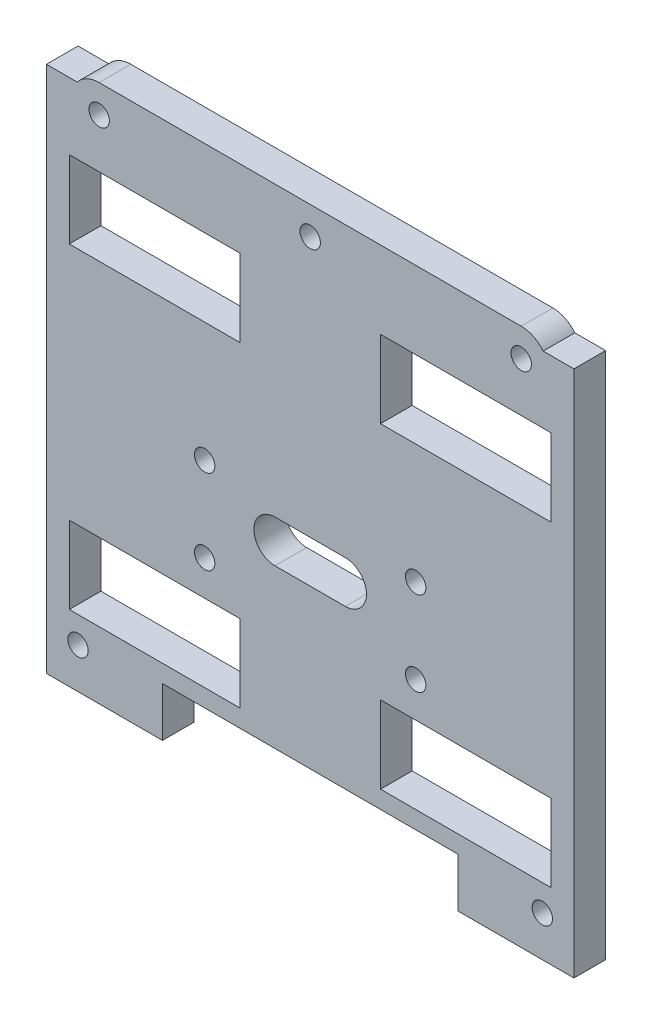
SolidWorks part; units mm, degrees
ref_plane "Front Plane" through (0, 0, 0) normal (0, 0, 1) x (1, 0, 0)
ref_plane "Top Plane" through (0, 0, 0) normal (0, 1, 0) x (1, 0, 0)
ref_plane "Right Plane" through (0, 0, 0) normal (1, 0, 0) x (0, 0, -1)
sketch "Sketch1" plane through (0, 0, 0) normal (0, 0, 1) x (1, 0, 0)
  line L0 (0, -37.5) -> (0, 37.5) construction
  line L1 (-47.5, -37.5) -> (47.5, -37.5)
  line L2 (-47.5, -37.5) -> (-47.5, 37.5)
  line L3 (-47.5, 37.5) -> (47.5, 37.5)
  line L4 (47.5, -37.5) -> (47.5, 37.5)
  line L5 (-47.5, -37.5) -> (47.5, 37.5) construction
  line L6 (-47.5, 37.5) -> (47.5, -37.5) construction
  line L7 (-47.5, 0) -> (47.5, 0) construction
  line L8 (-47.5, 22.5) -> (47.5, 22.5) construction
  line L9 (34.25, 17) -> (10, 28) construction
  line L10 (-34.25, 28) -> (-10, 28)
  line L11 (-34.25, 28) -> (-34.25, 17)
  line L12 (-34.25, 17) -> (-10, 17)
  line L13 (-10, 28) -> (-10, 17)
  line L14 (-34.25, 28) -> (-10, 17) construction
  line L15 (-34.25, 17) -> (-10, 28) construction
  line L16 (34.25, 28) -> (10, 17) construction
  line L17 (10, 28) -> (10, 17)
  line L18 (34.25, 17) -> (10, 17)
  line L19 (34.25, 28) -> (34.25, 17)
  line L20 (34.25, 28) -> (10, 28)
  line L21 (34.25, -28) -> (10, -17) construction
  line L22 (-34.25, -17) -> (-10, -28) construction
  line L23 (-34.25, -28) -> (-10, -17) construction
  line L24 (34.25, -17) -> (10, -28) construction
  line L25 (34.25, -28) -> (10, -28)
  line L26 (34.25, -28) -> (34.25, -17)
  line L27 (34.25, -17) -> (10, -17)
  line L28 (10, -28) -> (10, -17)
  line L29 (-10, -28) -> (-10, -17)
  line L30 (-34.25, -17) -> (-10, -17)
  line L31 (-34.25, -28) -> (-34.25, -17)
  line L32 (-34.25, -28) -> (-10, -28)
  point P0 (0, 0)
  point P12 (-22.125, 22.5)
  point P21 (22.125, 22.5)
  point P30 (22.125, -22.5)
  point P31 (-22.125, -22.5)
  dimension "D1" = 95
  dimension "D2" = 75
  dimension "D3" = 22.5
  dimension "D4" = 24.25
  dimension "D5" = 11
  dimension "D6" = 10
extrude "Boss-Extrude1" add sketch "Sketch1" along normal blind 4.5
sketch "Sketch8" plane through (0, 0, 4.5) normal (0, 0, 1) x (1, 0, 0)
  line L0 (-47.5, 37.5) -> (-47.5, -37.5) construction
  line L1 (47.5, -37.5) -> (47.5, 37.5) construction
  circle A0 centre (-47.5, 29.5) radius 8
  circle A1 centre (47.5, 29.5) radius 8
  dimension "D1" = 16
extrude "Boss-Extrude2" [suppressed] add sketch "Sketch8" against normal through all
sketch "Sketch2" plane through (0, 0, 4.5) normal (0, 0, 1) x (1, 0, 0)
  line L0 (0, -37.5) -> (0, 37.5) construction
  line L1 (-47.5, -37.5) -> (47.5, -37.5) construction
  line L2 (47.5, 37.5) -> (-47.5, 37.5) construction
  line L3 (-47.5, 0) -> (47.5, 0) construction
  line L4 (-47.5, 37.5) -> (-47.5, -37.5) construction
  line L5 (47.5, -37.5) -> (47.5, 37.5) construction
  line L6 (-40, 0) -> (40, 0) construction
  line L7 (-30, 35) -> (30, 35) construction
  circle A0 centre (-30, 35) radius 1.45
  circle A1 centre (30, 35) radius 1.45
  circle A2 centre (40, 0) radius 1.45
  circle A3 centre (-40, 0) radius 1.45
  circle A4 centre (0, 35) radius 1.45
  dimension "D1" = 2.9
  dimension "D7" = 2.9
  dimension "D8" = 2.9
  dimension "D9" = 2.9
  dimension "D2" = 30
  dimension "D3" = 35
  dimension "D4" = 80
  dimension "D5" = 40
  dimension "D6" = 0
extrude "screwHoles" cut sketch "Sketch2" against normal through all
sketch "Sketch3" plane through (0, 0, 4.5) normal (0, 0, 1) x (1, 0, 0)
  line L0 (-47.5, -20) -> (26.0486, -20) construction
  line L1 (-47.5, 37.5) -> (-47.5, -37.5) construction
  line L3 (0, 37.5) -> (0, -37.5) construction
  line L4 (47.5, 37.5) -> (-47.5, 37.5) construction
  line L5 (-47.5, -37.5) -> (47.5, -37.5) construction
  line L6 (18.95, -22.2) -> (9.05, -17.8) construction
  line L7 (-18.95, -17.8) -> (-9.05, -17.8)
  line L8 (-18.95, -17.8) -> (-18.95, -22.2)
  line L9 (-18.95, -22.2) -> (-9.05, -22.2)
  line L10 (-9.05, -17.8) -> (-9.05, -22.2)
  line L11 (-18.95, -17.8) -> (-9.05, -22.2) construction
  line L12 (-18.95, -22.2) -> (-9.05, -17.8) construction
  line L13 (18.95, -17.8) -> (9.05, -22.2) construction
  line L14 (9.05, -17.8) -> (9.05, -22.2)
  line L15 (18.95, -22.2) -> (9.05, -22.2)
  line L16 (18.95, -17.8) -> (18.95, -22.2)
  line L17 (18.95, -17.8) -> (9.05, -17.8)
  line L18 (-47.5, 37.5) -> (-47.5, -37.5) construction
  point P2 (-47.5, 0)
  point P12 (-14, -20)
  point P21 (14, -20)
  dimension "D1" = 9.9
  dimension "D3" = 14
  dimension "D4" = 20
extrude "BeltClamp" [suppressed] cut sketch "Sketch3" against normal through all
sketch "Sketch4" plane through (0, 0, 4.5) normal (0, 0, 1) x (1, 0, 0)
  line L0 (-47.5, 0) -> (47.5, 0) construction
  line L1 (-47.5, 37.5) -> (-47.5, -37.5) construction
  line L2 (47.5, -37.5) -> (47.5, 37.5) construction
  line L3 (0, 0) -> (0, 33.55) construction
  line L4 (-29.85, 2.175) -> (-20.15, 2.175)
  line L5 (-29.85, 2.175) -> (-29.85, -2.175)
  line L6 (-29.85, -2.175) -> (-20.15, -2.175)
  line L7 (-20.15, 2.175) -> (-20.15, -2.175)
  line L8 (-29.85, 2.175) -> (-20.15, -2.175) construction
  line L9 (-29.85, -2.175) -> (-20.15, 2.175) construction
  line L10 (29.85, -2.175) -> (20.15, 2.175) construction
  line L11 (29.85, 2.175) -> (20.15, -2.175) construction
  line L12 (20.15, 2.175) -> (20.15, -2.175)
  line L13 (29.85, -2.175) -> (20.15, -2.175)
  line L14 (29.85, 2.175) -> (29.85, -2.175)
  line L15 (29.85, 2.175) -> (20.15, 2.175)
  line L16 (-29.85, -2.175) -> (-20.15, 2.175) construction
  circle A0 centre (-40, 0) radius 1.45 construction
  circle A1 centre (0, 35) radius 1.45 construction
  point P6 (-25, 0)
  point P22 (25, 0)
  dimension "D3" = 0
  dimension "D2" = 4.35
  dimension "D4" = 25
extrude "Cut-Extrude3" [suppressed] cut sketch "Sketch4" against normal through all
sketch "Sketch5" plane through (0, 0, 4.5) normal (0, 0, 1) x (1, 0, 0)
  line L0 (-47.5, -9.75) -> (47.5, -9.75) construction
  line L1 (-47.5, 37.5) -> (-47.5, -37.5) construction
  line L2 (47.5, -37.5) -> (47.5, 37.5) construction
  line L4 (0, -37.5) -> (0, 37.5) construction
  line L5 (-47.5, -37.5) -> (47.5, -37.5) construction
  line L6 (47.5, 37.5) -> (-47.5, 37.5) construction
  line L7 (-30.825, -14.6) -> (-35.175, -4.9) construction
  line L8 (30.825, -4.9) -> (35.175, -4.9)
  line L9 (30.825, -4.9) -> (30.825, -14.6)
  line L10 (30.825, -14.6) -> (35.175, -14.6)
  line L11 (35.175, -4.9) -> (35.175, -14.6)
  line L12 (30.825, -4.9) -> (35.175, -14.6) construction
  line L13 (30.825, -14.6) -> (35.175, -4.9) construction
  line L14 (-30.825, -4.9) -> (-35.175, -14.6) construction
  line L15 (-35.175, -4.9) -> (-35.175, -14.6)
  line L16 (-30.825, -14.6) -> (-35.175, -14.6)
  line L17 (-30.825, -4.9) -> (-30.825, -14.6)
  line L18 (-30.825, -4.9) -> (-35.175, -4.9)
  line L19 (33, -9.75) -> (33, -37.5) construction
  line L20 (-33, -9.75) -> (-33, -37.5) construction
  line L21 (-33, -31.75) -> (33, -31.75) construction
  circle A0 centre (33, -31.75) radius 1.45
  circle A1 centre (-33, -31.75) radius 1.45
  point P15 (33, -9.75)
  point P24 (-33, -9.75)
  dimension "D5" = 2.9
  dimension "D2" = 9.7
  dimension "D3" = 4.35
  dimension "D4" = 33
  dimension "D6" = 22
  dimension "D1" = 9.75
extrude "Cut-Extrude4" [suppressed] cut sketch "Sketch5" against normal through all
sketch "Sketch9" plane through (0, 0, 4.5) normal (0, 0, 1) x (1, 0, 0)
  line L0 (47.5, 37.5) -> (-47.5, 37.5) construction
  line L1 (0, 37.5) -> (0, -37.5) construction
  line L2 (-47.5, -37.5) -> (47.5, -37.5) construction
  line L3 (50.5, 35) -> (45.5, 35) construction
  line L4 (-50.5, 35) -> (-45.5, 35) construction
  circle A0 centre (-30, 35) radius 4
  circle A1 centre (-30, 35) radius 1.45
  circle A2 centre (-30, 35) radius 1.45 construction
  circle A3 centre (30, 35) radius 1.45
  circle A4 centre (30, 35) radius 4
  point P17 (0, -37.5)
  dimension "D1" = 8
extrude "Boss-Extrude3" add sketch "Sketch9" against normal through all
sketch "Sketch10" plane through (0, 0, 4.5) normal (0, 0, 1) x (1, 0, 0)
  line L0 (-60, 37.5) -> (-37.5, 37.5)
  line L1 (-37.5, 37.5) -> (-37.5, -37.5)
  line L2 (-47.5, -37.5) -> (47.5, -37.5) construction
  line L3 (-37.5, -37.5) -> (-60, -37.5)
  line L4 (-60, -37.5) -> (-60, 37.5)
  line L5 (0, 37.5) -> (0, -37.5) construction
  line L6 (26.8775, 37.5) -> (-26.8775, 37.5) construction
  line L7 (60, -37.5) -> (60, 37.5)
  line L8 (37.5, -37.5) -> (60, -37.5)
  line L9 (37.5, 37.5) -> (37.5, -37.5)
  line L10 (60, 37.5) -> (37.5, 37.5)
  line L11 (-60, -37.5) -> (-60, 37.5)
  line L12 (-33.1225, 37.5) -> (-47.5, 37.5) construction
  line M3 (47.5, -37.5) -> (47.5, 37.5)
  line M7 (-47.5, 37.5) -> (-47.5, -37.5)
  line M8 (-47.5, -37.5) -> (47.5, -37.5)
  dimension "D3" = 0
  dimension "D1" = 75
  dimension "D2" = 60
extrude "Cut-Extrude5" cut sketch "Sketch10" against normal through all contours L1 L0 M7 M8 | L10 L9 M3 M8 region at (42.5, 0, 4.5) region at (-42.5, 0, 4.5)
sketch "Sketch11" plane through (0, 0, 4.5) normal (0, 0, 1) x (1, 0, 0)
  line L0 (-30, 39) -> (30, 39)
  line L1 (30, 39) -> (26.8775, 37.5)
  line L2 (26.8775, 37.5) -> (-26.8775, 37.5)
  line L3 (-26.8775, 37.5) -> (-30, 39)
  arc A0 (-26.8775, 37.5) -> (-33.1225, 37.5) centre (-30, 35) ccw construction
  arc A1 (33.1225, 37.5) -> (26.8775, 37.5) centre (30, 35) ccw construction
extrude "Boss-Extrude4" add sketch "Sketch11" against normal through all
sketch "Sketch12" plane through (0, 0, 4.5) normal (0, 0, 1) x (1, 0, 0)
  line L0 (-37.5, -12) -> (37.5, -12) construction
  line L1 (-37.5, 37.5) -> (-37.5, -37.5) construction
  line L2 (37.5, 37.5) -> (37.5, -37.5) construction
  line L3 (0, 0) -> (0, -37.5) construction
  line L4 (-37.5, -37.5) -> (37.5, -37.5) construction
  circle A0 centre (-15, -12) radius 1.45
  circle A1 centre (15, -12) radius 1.45
  dimension "D2" = 2.9
  dimension "D1" = 15
  dimension "D3" = 12
extrude "FanBraceScrews" cut sketch "Sketch12" against normal through all
sketch "Sketch13" plane through (0, 0, 4.5) normal (0, 0, 1) x (1, 0, 0)
  line L0 (-37.5, -37.5) -> (37.5, -37.5) construction
  line L1 (-21, -44.5) -> (21, -44.5)
  line L2 (-21, -44.5) -> (-21, -30.5)
  line L3 (-21, -30.5) -> (21, -30.5)
  line L4 (21, -44.5) -> (21, -30.5)
  line L5 (-21, -44.5) -> (21, -30.5) construction
  line L6 (-21, -30.5) -> (21, -44.5) construction
  point P0 (0, -37.5)
  dimension "D1" = 42
  dimension "D2" = 7
extrude "Cut-Extrude7" cut sketch "Sketch13" against normal through all
sketch "Sketch20" plane through (0, 0, 0) normal (0, 0, -1) x (-1, 0, 0)
  line L0 (15, -10.55) -> (15, 0) construction
  line L1 (0, 0) -> (0, 8.2059) construction
  line L2 (-15, -10.55) -> (-15, 0) construction
  circle A0 centre (15, -12) radius 1.45 construction
  circle A1 centre (15, 0) radius 1.45
  circle A2 centre (-15, 0) radius 1.45
  dimension "D1" = 12
extrude "Cut-Extrude11" cut sketch "Sketch20" against normal through all
sketch "Sketch14" plane through (0, 0, 4.5) normal (0, 0, 1) x (1, 0, 0)
  line L0 (15, -13.45) -> (15, 0) construction
  line L1 (0, 0) -> (0, -40.3958) construction
  line L2 (-15, -13.45) -> (-15, 0) construction
  circle A0 centre (15, -12) radius 1.45 construction
  circle A1 centre (15, 0) radius 1.45
  circle A2 centre (-15, 0) radius 1.45
  dimension "D2" = 2.9
  dimension "D1" = 12
extrude "Cut-Extrude8" [suppressed] cut sketch "Sketch14" against normal through all
sketch "Sketch15" plane through (0, 0, 4.5) normal (0, 0, 1) x (1, 0, 0)
  line L0 (-25, 1.5) -> (-25, -10.5) construction
  line L2 (0, 0) -> (0, -11.0705) construction
  line L3 (16, -8.3509) -> (25, -10.5) construction
  line L4 (25, 1.5) -> (25, -10.5) construction
  circle A0 centre (-25, 1.5) radius 1.45
  circle A1 centre (-25, -10.5) radius 1.45
  circle A2 centre (25, -10.5) radius 1.45
  circle A3 centre (25, 1.5) radius 1.45
  circle A5 centre (-15, -12) radius 1.45 construction
  dimension "D1" = 12
  dimension "D3" = 2.9
  dimension "D4" = 2.9
  dimension "D2" = 25
  dimension "D5" = 1.5
extrude "BeltClipScrews" [suppressed] cut sketch "Sketch15" against normal through all
sketch "Sketch16" [suppressed] plane through (0, 0, 4.5) normal (0, 0, 1) x (1, 0, 0)
  line L0 (0, 0) -> (0, -11.3016) construction
  line L1 (-29.85, 2.175) -> (-20.15, 2.175)
  line L2 (-29.85, 2.175) -> (-29.85, -2.175)
  line L3 (-29.85, -2.175) -> (-20.15, -2.175)
  line L4 (-20.15, 2.175) -> (-20.15, -2.175)
  line L5 (-35.175, -4.9) -> (-30.825, -4.9)
  line L6 (-35.175, -4.9) -> (-35.175, -14.6)
  line L7 (-35.175, -14.6) -> (-30.825, -14.6)
  line L8 (-30.825, -4.9) -> (-30.825, -14.6)
  line L9 (30.825, -4.9) -> (30.825, -14.6)
  line L10 (35.175, -14.6) -> (30.825, -14.6)
  line L11 (35.175, -4.9) -> (35.175, -14.6)
  line L12 (35.175, -4.9) -> (30.825, -4.9)
  line L13 (20.15, 2.175) -> (20.15, -2.175)
  line L14 (29.85, -2.175) -> (20.15, -2.175)
  line L15 (29.85, 2.175) -> (29.85, -2.175)
  line L16 (29.85, 2.175) -> (20.15, 2.175)
  line L17 (-30.825, -4.9) -> (-30.825, -14.6)
extrude "Boss-Extrude5" [suppressed] add sketch "Sketch16" against normal through all contours L8 L5 L6 L7 | L4 L1 L2 L3 | L15 L16 L13 L14 | L11 L12 L9 L10
sketch "Sketch17" [suppressed] plane through (0, 0, 4.5) normal (0, 0, 1) x (1, 0, 0)
  line L0 (0, -30.5) -> (0, 0) construction
  line L1 (21, -30.5) -> (-21, -30.5) construction
  line L2 (-37.5, -37.5) -> (-46.5, -37.5)
  line L3 (-46.5, -37.5) -> (-46.5, -22.5)
  line L4 (-46.5, -22.5) -> (-43.5, -22.5)
  line L5 (-43.5, -22.5) -> (-43.5, -32.5)
  line L6 (-43.5, -32.5) -> (-37.5, -32.5)
  line L7 (-37.5, 37.5) -> (-37.5, -37.5) construction
  line L8 (-37.5, -32.5) -> (-37.5, -37.5)
  line L9 (-37.5, -37.5) -> (-37.5303, -37.4889)
  dimension "D1" = 3
  dimension "D2" = 6
  dimension "D3" = 5
  dimension "D4" = 15
extrude "Boss-Extrude6" [suppressed] add sketch "Sketch17" against normal through all contours L8 L6 L5 L4 L3 L2
sketch "Sketch18" plane through (0, 0, 0) normal (0, 0, 1) x (1, 0, 0)
  line L0 (0, -30.5) -> (0, 0) construction
  line L1 (-37.5, -37.5) -> (-21, -37.5) construction
  line L7 (-37.5, -27.5) -> (-37.5, -22.5)
  line L9 (-43.5, -27.5) -> (-37.5, -27.5)
  line L10 (-37.5, -30) -> (-45.5, -30) construction
  line L11 (-37.5, 37.5) -> (-37.5, -37.5) construction
  line L12 (-43.5, -37.5) -> (-43.5, -27.5)
  line L13 (-46.5, -37.5) -> (-43.5, -37.5)
  line L14 (-46.5, -22.5) -> (-46.5, -37.5)
  line L15 (-37.5, -22.5) -> (-46.5, -22.5)
  dimension "D1" = 6
  dimension "D2" = 15
  dimension "D3" = 5
extrude "Boss-Extrude7" [suppressed] add sketch "Sketch18" along normal through all
mirror "Mirror1" [suppressed] about plane through (0, 0, 0) normal (1, 0, 0)
fillet "Fillet1" [suppressed] radius 2
mirror "Mirror2" [suppressed] about plane through (0, 0, 0) normal (1, 0, 0)
fillet "Fillet2" [suppressed] radius 2
sketch "Sketch19" plane through (0, 0, 4.5) normal (0, 0, 1) x (1, 0, 0)
  line L0 (-5, -5) -> (5, -5) construction
  line L1 (-5, -2) -> (5, -2)
  line L2 (-5, -8) -> (5, -8)
  line L3 (0, 0) -> (0, -15.8058) construction
  arc A0 (-5, -2) -> (-5, -8) centre (-5, -5) ccw
  arc A1 (5, -8) -> (5, -2) centre (5, -5) ccw
  point P2 (0, -5)
  dimension "D1" = 10
  dimension "D2" = 6
  dimension "D3" = 0
  dimension "D4" = 5
extrude "Cut-Extrude9" cut sketch "Sketch19" against normal through all
sketch "Sketch21" plane through (0, 0, 0) normal (0, 0, -1) x (-1, 0, 0)
  line L0 (0, 0) -> (0, -30.5) construction
  line L1 (-21, -30.5) -> (21, -30.5) construction
  circle A0 centre (-33, -31.75) radius 1.45
  circle A1 centre (33, -31.75) radius 1.45
  dimension "D1" = 2.9
  dimension "D2" = 33
  dimension "D3" = 31.75
extrude "Cut-Extrude12" cut sketch "Sketch21" against normal through all
equation "\"X-ROD-SPACING\"=45"
equation "\"Y-ROD-SPACING\"=75"
equation "\"Z-ROD-SPACING\"=17.5"
equation "\"Y-BED-OFFSET\"=2"
equation "\"Y-BED-ROD-INSET\"=3.5"
equation "\"Y-BED-SCREW-SPACING\"=209"
equation "\"Y-BED-SCREW-CUTOUT-SLOT-HEIGHT\"=2.5"
equation "\"T-SLOT-NUT-FILLET-RADIUS\"=0.5"
equation "\"T-SLOT-SCREW-SHAFT-RADIUS\"=1.55"
equation "\"T-SLOT-SCREW-SHAFT-CUTOUT-LENGTH\"=11"
equation "\"T-SLOT-NUT-DEPTH\"=3.5"
equation "\"T-SLOT-NUT-WIDTH\"=2.85"
equation "\"T-SLOT-NUT-END-DISTANCE\"=8"
equation "\"ACRYLIC-THICKNESS\"=10"
equation "\"ACRYLIC-THICKNESS2\"=4.5"
equation "\"ACRYLIC-TAB-CUTOUT-SIZE\"=\"ACRYLIC-THICKNESS\"+\"ACRYLIC-TAB-TOLERANCE\"*2"
equation "\"ACRYLIC-TAB-WIDTH\"=\"ACRYLIC-THICKNESS\""
equation "\"ACRYLIC-M3-HOLE\"=2.9"
equation "\"SMOOTHROD-CAP-SCREW-DISTANCE\"=20"
equation "\"FRAME-WIDTH-INNER\"=370"
equation "\"NEMA17-HOLE-SPACING\"=31"
equation "\"NEMA17-CENTRAL-CUTOUT\"=22.5"
equation "\"Z-BRACKET-REACH\"=57"
equation "\"Z-ROD-INSET\"=13.5"
equation "\"TOP-BRACKET-SPACING\"=40"
equation "\"SMOOTHROD-X-LENGTH\"=350"
equation "\"SMOOTHROD-Y-LENGTH\"=350"
equation "\"SMOOTHROD-Z-LENGTH\"=350"
equation "\"SMOOTHROD-TIGHTENING-HEADROOM\"=.25"
equation "\"LEADSCREW-Z-LENGTH\"=300"
equation "\"SCREW-LENGTH-FRAME\"=\"ACRYLIC-THICKNESS\" + 10"
equation "\"SCREW-LENGTH-MOTOR\"=\"ACRYLIC-THICKNESS\" + 5"
equation "\"SCREW-HEAD-RADIUS\"=6"
equation "\"PRINTED-X-SMOOTHROD-DIAMETER\"=8.8"
equation "\"PRINTED-X-SMOOTHROD-CUTOUT\"=10"
equation "\"PRINTED-X-BASE-HEIGHT\"=10"
equation "\"PRINTED-LM8UU-CUTOUT-SIZE\"=15.5"
equation "\"PRINTED-LM8UU-CUTOUT-LENGTH\"=24.5"
equation "\"PRINTED-X-IDLER-HEIGHT\"=16"
equation "\"PSU-MOUNTING-WIDTH\"=50"
equation "\"PSU-MOUNTING-HEIGHT\"=150"
equation "\"Y-BELT-TO-ROD-DISTANCE\"=20"
equation "\"SPOOL-HOLDER-ROD-SPACING\"=150"
equation "\"D3@Sketch1\"=\"X-ROD-SPACING\"/2"
equation "\"D4@Sketch1\"=\"ACRYLIC-X-CARRIAGE-LM8UU-CUTOUT-WIDTH\""
equation "\"D1@Boss-Extrude1\"=\"ACRYLIC-THICKNESS2\""
equation "\"D1@Sketch2\"=\"ACRYLIC-M3-HOLE\""
equation "\"D1@Sketch3\"=\"ACRYLIC-TAB-CUTOUT-SIZE\""
equation "\"D2@Sketch3\"=\"ACRYLIC-THICKNESS2\"+\"ACRYLIC-TAB-TOLERANCE\"*2"
equation "\"ACRYLIC-X-CARRIAGE-WIDTH\"=55"
equation "\"ACRYLIC-X-CARRIAGE-HEIGHT\"=75"
equation "\"D2@Sketch1\"=\"ACRYLIC-X-CARRIAGE-HEIGHT\""
equation "\"ACRYLIC-X-CARRIAGE-CENTER-TAB-SPACING\"=14"
equation "\"D3@Sketch3\"=\"ACRYLIC-X-CARRIAGE-CENTER-TAB-SPACING\""
equation "\"SCREW-LENGTH-EXTRUDER\"=28"
equation "\"ACRYLIC-X-CARRIAGE-SCREW-SPACING-X\"=15"
equation "\"ACRYLIC-X-CARRIAGE-SCREW-SPACING-Y\"=33"
equation "\"D1@Sketch4\"=\"ACRYLIC-TAB-WIDTH\"-\"KERF\"*4"
equation "\"D2@Sketch4\"=\"ACRYLIC-THICKNESS2\"-\"KERF\"*2"
equation "\"D2@Sketch5\"=\"ACRYLIC-TAB-WIDTH\"-\"KERF\"*4"
equation "\"D3@Sketch5\"=\"ACRYLIC-THICKNESS2\"-\"KERF\"*2"
equation "\"ACRYLIC-X-CARRIAGE-EXTRUDER-SHELF-DEPTH\"=\"ACRYLIC-X-CARRIAGE-EXTRUDER-OFFSET\" + 28"
equation "\"ACRYLIC-X-CARRIAGE-EXTRUDER-BRACE-SPACING\"=23"
equation "\"D4@Sketch5\"=\"ACRYLIC-X-CARRIAGE-DUAL-MOUNT-BRACE-WIDTH\""
equation "\"D1@Sketch5\"=\"ACRYLIC-THICKNESS2\"/2 + 7.5"
equation "\"D4@Sketch2\"=\"ACRYLIC-X-CARRIAGE-DUAL-MOUNT-SCREW-WIDTH\"*2"
equation "\"D5@Sketch2\"=\"ACRYLIC-X-CARRIAGE-DUAL-MOUNT-SCREW-WIDTH\""
equation "\"D7@Sketch2\"=\"ACRYLIC-M3-HOLE\""
equation "\"D8@Sketch2\"=\"ACRYLIC-M3-HOLE\""
equation "\"ACRYLIC-X-CARRIAGE-LM8UU-CUTOUT-WIDTH\"=24.25"
equation "\"ACRYLIC-TAB-TOLERANCE\"=-.05"
equation "\"ACRYLIC-X-CARRIAGE-EXTRUDER-OFFSET\"=26"
equation "\"ACRYLIC-X-CARRIAGE-EXTRUDER-ANGLE\"=90"
equation "\"ACRYLIC-X-CARRIAGE-EXTRUDER-BRACE-TAB-OFFSET\"=20"
equation "\"ACRYLIC-X-CARRIAGE-EXTRUDER-BRACE-HEIGHT\"=35"
equation "\"ACRYLIC-X-CARRIAGE-EXTRUDER-BRACE-SCREW-SPACING\"=22"
equation "\"D5@Sketch5\"=\"ACRYLIC-M3-HOLE\""
equation "\"ACRYLIC-X-CARRIAGE-DUAL-WIDTH-MULTIPLIER\"=1.65"
equation "\"ACRYLIC-X-CARRIAGE-DUAL-HOTEND-SPACING\"=42"
equation "\"ACRYLIC-X-CARRIAGE-DUAL-WIDTH\"=75"
equation "\"ACRYLIC-X-CARRIAGE-DUAL-HOTEND-SEPARATION\"=36"
equation "\"ACRYLIC-X-CARRIAGE-DUAL-MOUNT-PLATE-DEPTH\"=75"
equation "\"ACRYLIC-X-CARRIAGE-DUAL-MOUNT-BRACE-WIDTH\"=33"
equation "\"ACRYLIC-X-CARRIAGE-DUAL-MOUNT-SCREW-WIDTH\"=40"
equation "\"D9@Sketch2\"=\"ACRYLIC-M3-HOLE\""
equation "\"ACRYLIC-X-CARRIAGE-LM8UU-CUTOUT-HEIGHT\"=11.0"
equation "\"D5@Sketch1\"=\"ACRYLIC-X-CARRIAGE-LM8UU-CUTOUT-HEIGHT\""
equation "\"D1@Sketch10\"=\"ACRYLIC-X-CARRIAGE-DUAL-WIDTH\""
equation "\"D2@Sketch12\"=\"ACRYLIC-M3-HOLE\""
equation "\"D2@Sketch14\"=\"ACRYLIC-M3-HOLE\""
equation "\"D3@Sketch15\"=\"ACRYLIC-M3-HOLE\""
equation "\"D4@Sketch15\"=\"ACRYLIC-M3-HOLE\""
equation "\"KERF\"=0.075"
equation "\"ACRYLIC-THICKNESS-TAB-CUTOUT-WIDTH\"=\"ACRYLIC-THICKNESS\"-\"KERF\"*2"
equation "\"ACRYLIC-THICKNESS-TAB-CUTOUT-HEIGHT\"=\"ACRYLIC-TAB-WIDTH\"-\"KERF\"*4"
equation "\"ACRYLIC-THICKNESS2-TAB-CUTOUT-WIDTH\"=\"ACRYLIC-THICKNESS2\"-\"KERF\"*2"
equation "\"ACRYLIC-THICKNESS2-TAB-CUTOUT-HEIGHT\"=\"ACRYLIC-TAB-WIDTH\"-\"KERF\"*4"
equation "\"PRINTED-M3-HOLE\"=3.5"
equation "\"PRINTED-M3-NUT-AF\"=6.25"
equation "\"ACRYLIC-X-CARRIAGE-DUAL-FAN-OFFSET\"=52"
equation "\"ACRYLIC-X-CARRIAGE-DUAL-FAN-HEIGHT\"=20"
equation "\"BLOWER-FAN-WIDTH\"=15"
equation "\"D1@Sketch21\"=\"ACRYLIC-M3-HOLE\""
equation "\"D2@Sketch21\"=\"ACRYLIC-X-CARRIAGE-DUAL-MOUNT-BRACE-WIDTH\""
equation "\"D3@Sketch21\"=\"ACRYLIC-THICKNESS2\"/2 + 7.5+22"
